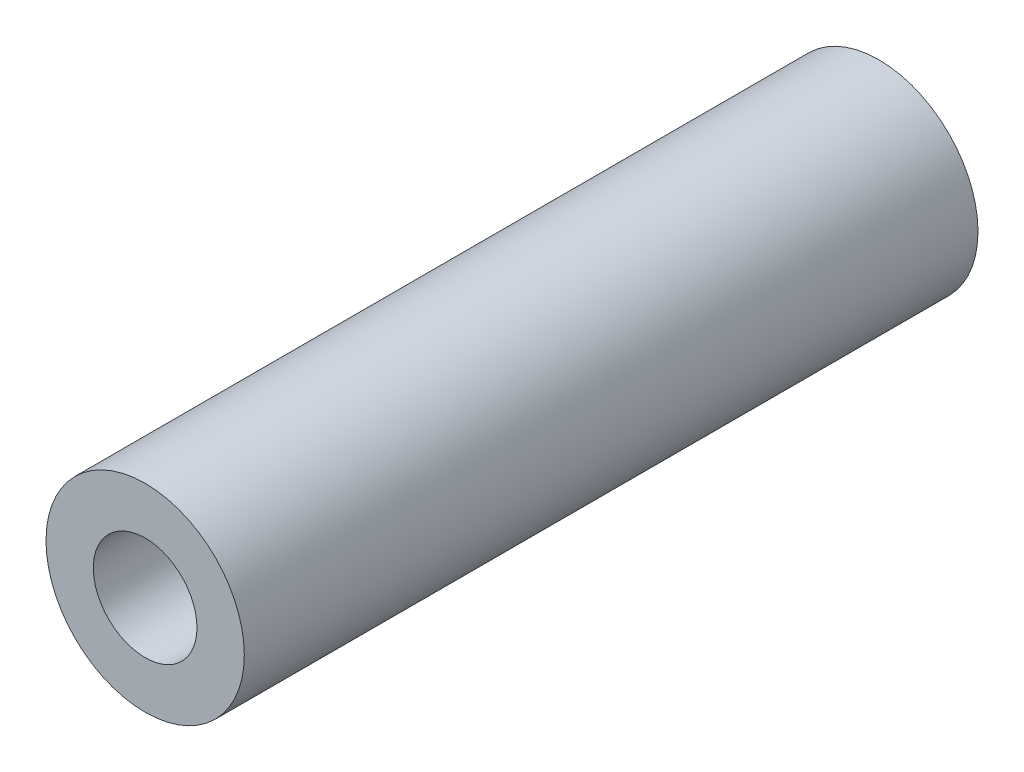
SolidWorks part; units mm, degrees
ref_plane "Front Plane" through (0, 0, 0) normal (0, 0, 1) x (1, 0, 0)
ref_plane "Top Plane" through (0, 0, 0) normal (0, 1, 0) x (1, 0, 0)
ref_plane "Right Plane" through (0, 0, 0) normal (1, 0, 0) x (0, 0, -1)
sketch "Sketch1" plane through (0, 0, 0) normal (0, 0, 1) x (1, 0, 0)
  circle A0 centre (0, 0) radius 4.7625
  circle A1 centre (0, 0) radius 2.4892
  dimension "D1" = 9.525
  dimension "D2" = 4.9784
extrude "Boss-Extrude1" add sketch "Sketch1" along normal mid plane 35.2425
